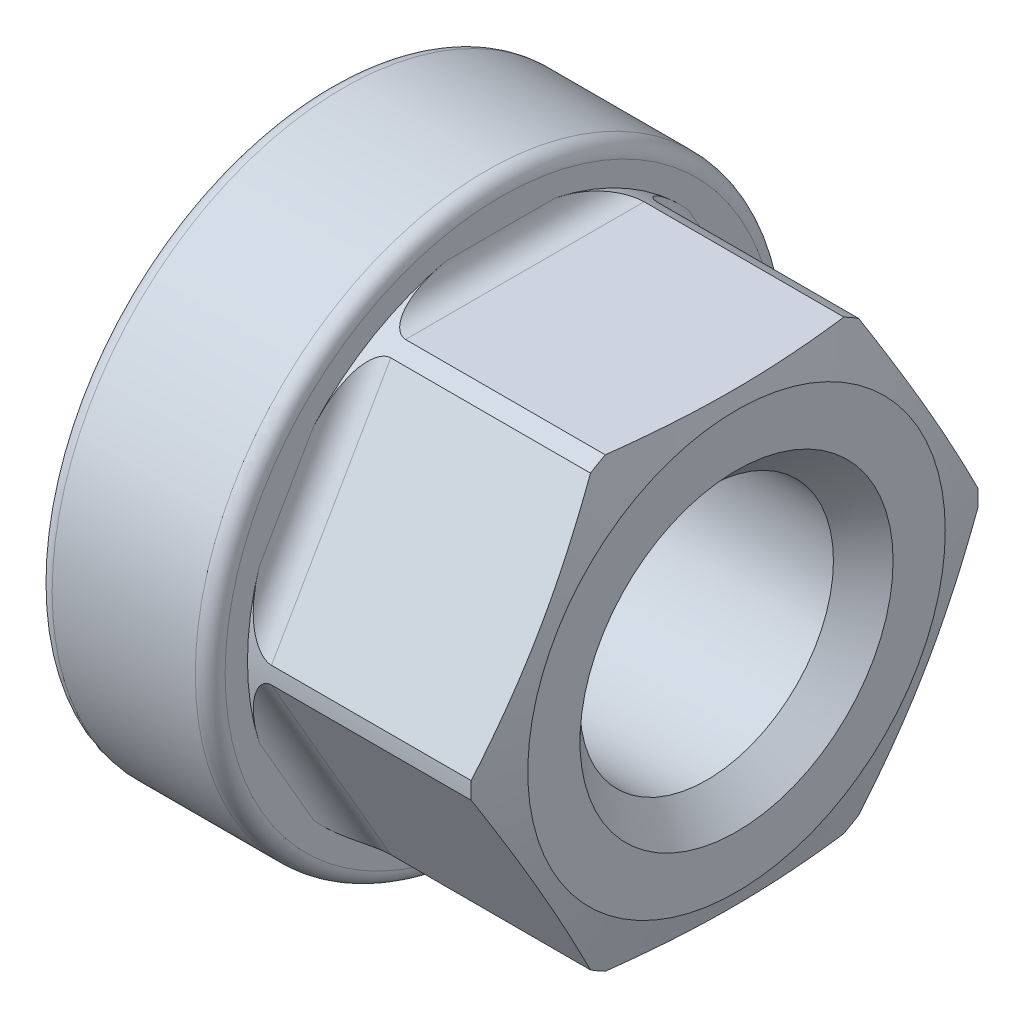
SolidWorks part; units mm, degrees
material "4140"
ref_plane "Front Plane" through (0, 0, 0) normal (0, 0, 1) x (1, 0, 0)
ref_plane "Top Plane" through (0, 0, 0) normal (0, 1, 0) x (1, 0, 0)
ref_plane "Right Plane" through (0, 0, 0) normal (1, 0, 0) x (0, 0, -1)
sketch "Sketch1" plane through (0, 0, 0) normal (0, 0, 1) x (1, 0, 0)
  line L0 (0, 5.25) -> (0, 7)
  line L1 (-0.4019, 8.5) -> (-7.9, 8.5)
  line L2 (-7.9, 8.5) -> (-7.9, 9.75)
  line L3 (-7.9, 9.75) -> (-13.7, 9.75)
  line L4 (-13.7, 9.75) -> (-13.7, 5.25)
  line L5 (-12.7, 4.25) -> (-1, 4.25)
  line L6 (0, 0) -> (-13.7, 0) construction
  line L7 (-0.4019, 8.5) -> (0, 7)
  line L8 (-1, 4.25) -> (0, 5.25)
  line L9 (-13.7, 5.25) -> (-12.7, 4.25)
  point P0 (0, 4.25)
  point P6 (-13.7, 4.25)
  dimension "D1" = 13.7
  dimension "D2" = 5.8
  dimension "D3" = 17
  dimension "D4" = 19.5
  dimension "D5" = 8.5
  dimension "D6" = 15
  dimension "D7" = 14
revolve "Revolve1" add sketch "Sketch1" angle 360 about L6
cosmetic thread "Cosmetic Thread1" parameters "D2"=10
sketch "Sketch2" plane through (0, 0, 0) normal (1, 0, 0) x (0, 0, -1)
  line L1 (8.6603, 0) -> (4.3301, 7.5)
  line L2 (4.3301, 7.5) -> (-4.3301, 7.5)
  line L3 (-4.3301, 7.5) -> (-8.6603, 0)
  line L4 (-8.6603, 0) -> (-4.3301, -7.5)
  line L5 (-4.3301, -7.5) -> (4.3301, -7.5)
  line L6 (4.3301, -7.5) -> (8.6603, 0)
  circle A0 centre (0, 0) radius 7.5 construction
extrude "Cut-Extrude1" cut sketch "Sketch2" against normal up to surface (7.9 mm away) flip side to cut up to face at (-7.9, 0, -9.75)
fillet "Fillet1" radius 0.5 2 edges at (-13.7, 0, -9.75) (-7.9, 0, -9.75)
fillet "Fillet2" radius 0.8 6 edges at (-7.9, -3.75, 6.4952) (-7.9, -7.5, 0) (-7.9, -3.75, -6.4952) (-7.9, 3.75, -6.4952) (-7.9, 7.5, 0) (-7.9, 3.75, 6.4952)
